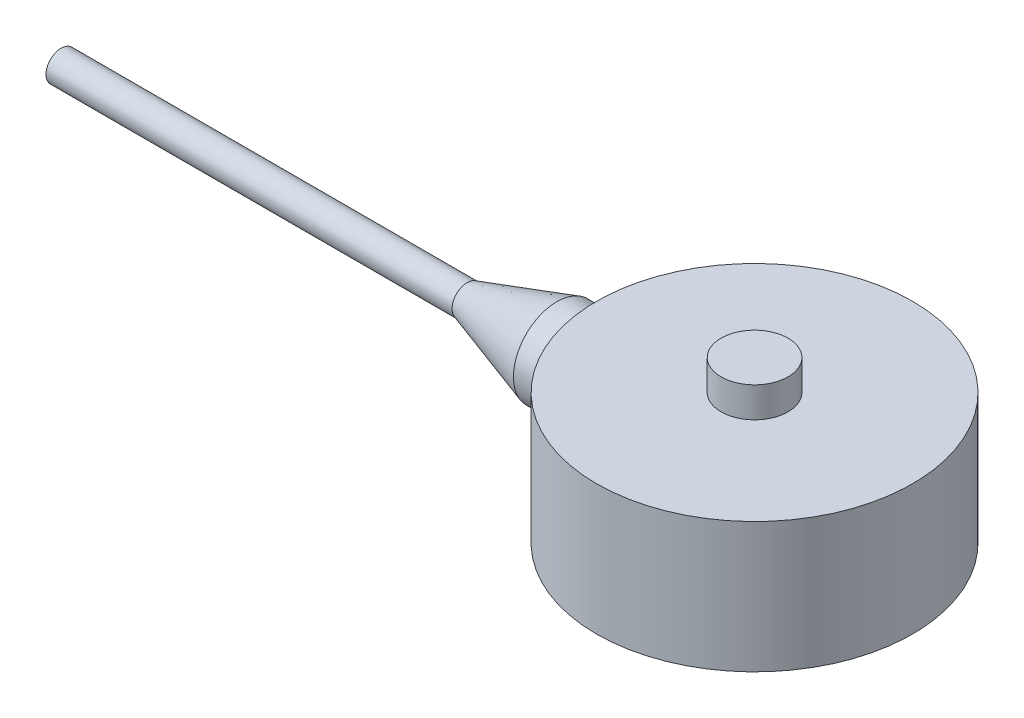
SolidWorks part; units mm, degrees
ref_plane "Front Plane" through (0, 0, 0) normal (0, 0, 1) x (1, 0, 0)
ref_plane "Top Plane" through (0, 0, 0) normal (0, 1, 0) x (1, 0, 0)
ref_plane "Right Plane" through (0, 0, 0) normal (1, 0, 0) x (0, 0, -1)
sketch "Sketch1" plane through (0, 0, 0) normal (0, 1, 0) x (1, 0, 0)
  circle A0 centre (0, 0) radius 25
  dimension "D1" = 50
extrude "base" add sketch "Sketch1" along normal blind 20.6
sketch "Sketch2" plane through (0, 20.6, 0) normal (0, 1, 0) x (1, 0, 0)
  circle A0 centre (0, 0) radius 5.3
  dimension "D1" = 10.6
extrude "button" add sketch "Sketch2" along normal blind 4.8
sketch "Sketch3" plane through (0, 0, 0) normal (0, 0, 1) x (1, 0, 0)
  line L0 (-17.472, 10.5324) -> (-109.698, 10.5324) construction
  line L3 (-31.279, 17.4046) -> (-45.4686, 12.9245)
  line L4 (-17.472, 10.5324) -> (-17.472, 17.4046)
  line L5 (-45.4686, 12.9245) -> (-109.698, 12.9245)
  line L6 (-109.698, 12.9245) -> (-109.698, 10.5324)
  line L7 (-17.472, 10.5324) -> (-109.698, 10.5324)
  line L9 (-25, 17.4046) -> (-25, 10.5324) construction
  line L10 (-25, 10.5324) -> (-17.472, 10.5324)
  line L11 (-25, 20.6) -> (-25, 0) construction
  line L12 (-31.279, 17.4046) -> (-25, 17.4046)
  line L13 (-25, 17.4046) -> (-17.472, 17.4046)
  point P2 (-109.698, 10.5324)
revolve "cable" add sketch "Sketch3" angle 360 about L7
